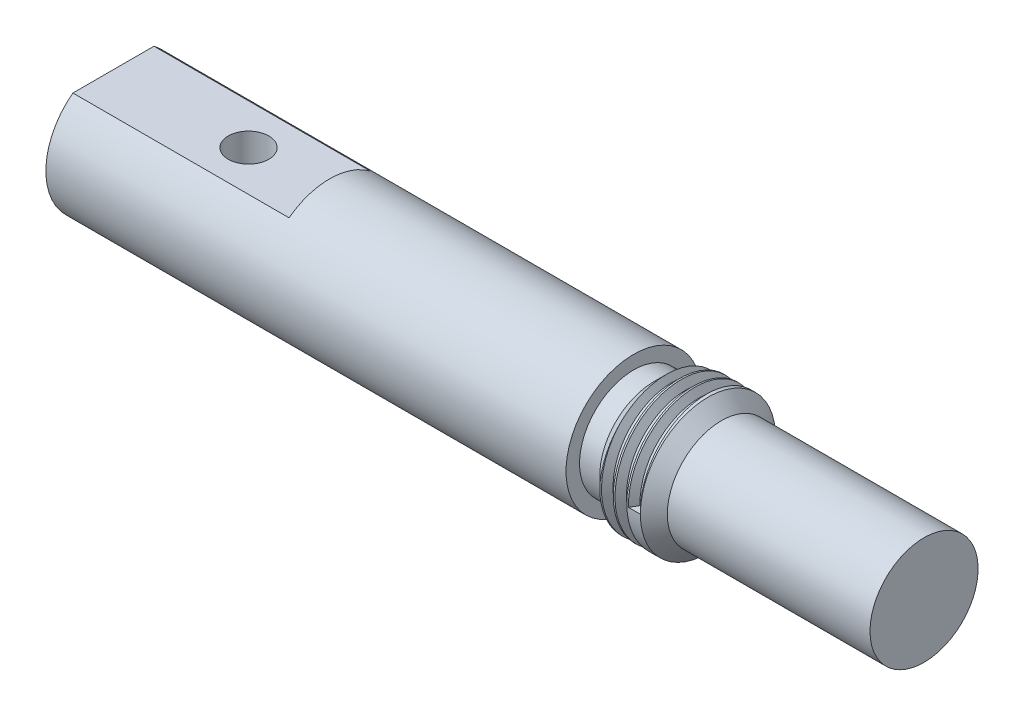
SolidWorks part; units mm, degrees
ref_plane "Front Plane" through (0, 0, 0) normal (0, 0, 1) x (1, 0, 0)
ref_plane "Top Plane" through (0, 0, 0) normal (0, 1, 0) x (1, 0, 0)
ref_plane "Right Plane" through (0, 0, 0) normal (1, 0, 0) x (0, 0, -1)
sketch "Sketch1" plane through (0, 0, 0) normal (0, 0, 1) x (1, 0, 0)
  line L0 (0, 0) -> (4.9597, 0) construction
  line L1 (0, 0) -> (0, 5)
  line L2 (0, 5) -> (45, 5)
  line L3 (60, 4) -> (60, 0)
  line L4 (0, 0) -> (60, 0)
  line L5 (45, 5) -> (45, 4)
  line L6 (45, 4) -> (60, 4)
  dimension "D1" = 5
  dimension "D2" = 4
  dimension "D3" = 60
  dimension "D4" = 15
revolve "Revolve1" add sketch "Sketch1" angle 360 about L0
sketch "Sketch2" plane through (0, 0, 0) normal (-1, 0, 0) x (0, 0, 1)
  line L0 (3, 4) -> (-3, 4)
  line L1 (-3, 4) -> (-3, -4) construction
  line L2 (-3, -4) -> (3, -4)
  line L3 (3, -4) -> (3, 4) construction
  circle A1 centre (0, 0) radius 5
  circle A2 centre (0, 0) radius 5 construction
  dimension "D1" = 8
extrude "Cut-Extrude1" cut sketch "Sketch2" against normal blind 16 contours L0 | L2 region at (0, 4.4036, 0) region at (0, -4.4036, 0)
sketch "Sketch8" plane through (0, 4, 0) normal (0, 1, 0) x (1, 0, 0)
  point P0 (10, 0)
  dimension "D1" = 10
hole_wizard "Ø3.0mm Dowel Hole1" positions "Sketch8" profile "Sketch7" hole size "Ø3.0" standard "DIN" end condition through all
sketch "Sketch7" plane through (10, 4, 0) normal (1, 0, 0) x (0, 0, 1)
  line L0 (0, 0) -> (0, 9)
  line L1 (0, 9) -> (1.5, 9)
  line L2 (1.5, 9) -> (1.5, 0)
  line L5 (1.5, 0) -> (0, 0)
  line L11 (0, -6.35) -> (0, 107.95) construction
  dimension "Thru Hole Dia." = 3
  dimension "Thru Hole Depth" = 9
sketch "Sketch17" plane through (60, 0, 0) normal (1, 0, 0) x (0, 0, -1)
  circle A0 centre (0, 0) radius 5 construction
  circle A2 centre (0, 0) radius 5
  circle A4 centre (0, 0) radius 4
  dimension "D1" = 8
extrude "Cut-Extrude3" cut sketch "Sketch17" against normal blind 1.5 from offset 20 offset against normal yes
chamfer "Chamfer2" distance 1 angle 45 2 edges at (45, 0, 5) (40, 0, -5)
thread "Thread2" pitch 1 method cut profile "Thread Profile2" start angle 0, offset 0, length 0, pitch 1, diameter 10
ref_plane "Plane4" through (44, 0, 5) normal (0, -1, 0) x (0, 0, 1)
sketch "Thread Profile2" plane through (44, 0, 5) normal (0, -1, 0) x (0, 0, 1)
  line L0 (0, 0) -> (0, 1) construction
  line L11 (0, 0) -> (0, 0.875)
  line L12 (0, 0.875) -> (-0.5413, 0.5625)
  line L13 (-0.5413, 0.5625) -> (-0.5413, 0.3125)
  line L15 (-0.5413, 0.3125) -> (0, 0)
  line L17 (-0.5413, 0.4375) -> (0, 0.4375) construction
  point P2 (0, 0)
  dimension "Pitch" = 1
  dimension "Profile_Angle" = 60
  dimension "Profile_Land" = 0.25
  dimension "Profile_Height" = 0.5413
